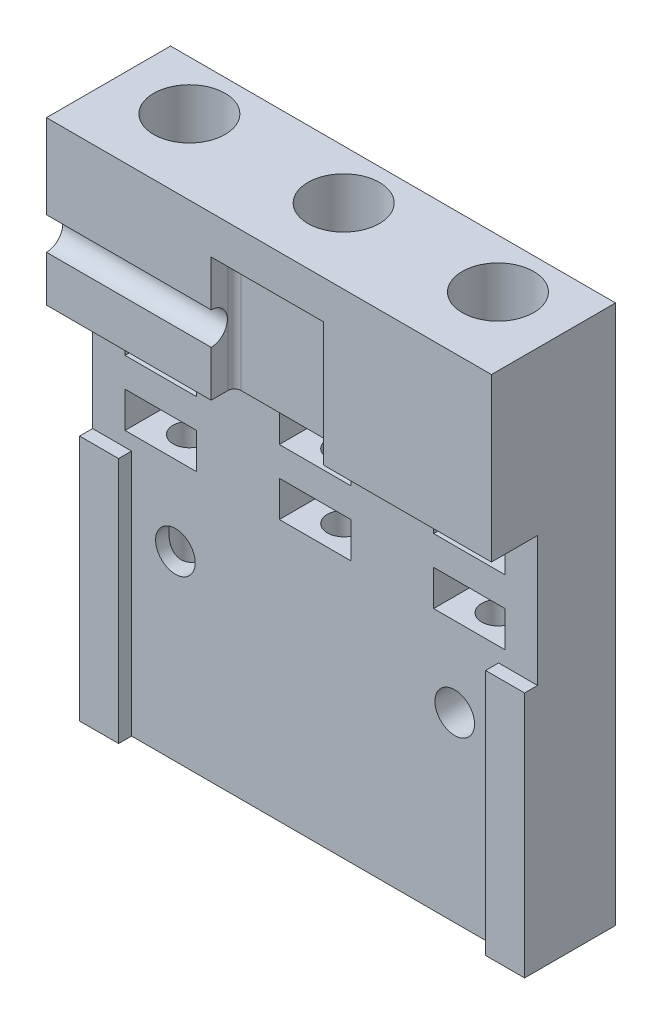
SolidWorks part; units mm, degrees
ref_plane "Plan de face" through (0, 0, 0) normal (0, 0, 1) x (1, 0, 0)
ref_plane "Plan de dessus" through (0, 0, 0) normal (0, 1, 0) x (1, 0, 0)
ref_plane "Plan de droite" through (0, 0, 0) normal (1, 0, 0) x (0, 0, -1)
sketch "Esquisse2" plane through (0, 0, 0) normal (0, 0, 1) x (1, 0, 0)
  line L0 (-28.25, 19) -> (28.25, -19) construction
  line L1 (-28.25, 19) -> (28.25, 19)
  line L2 (-28.25, 19) -> (-28.25, -19)
  line L3 (-28.25, -19) -> (28.25, -19)
  line L4 (28.25, 19) -> (28.25, -19)
  line L5 (0, 0) -> (0, 57.7917) construction
  line L6 (-34.25, 19) -> (-28.25, 19)
  line L8 (-28.25, 19) -> (-28.25, -19)
  line L10 (-34.25, 19) -> (-34.25, -19)
  line L11 (34.25, 19) -> (34.25, -19)
  line L12 (-34.25, -19) -> (-28.25, -19)
  line L13 (28.25, -19) -> (34.25, -19)
  line L14 (28.25, 19) -> (34.25, 19)
  circle A0 centre (-21.5, 9) radius 3.05
  circle A1 centre (21.5, 9) radius 3.05
  point P5 (0, 0)
  dimension "D3" = 6.1
  dimension "D4" = 10
  dimension "D6" = 6
  dimension "D5" = 21.5
  dimension "D1" = 38
  dimension "D2" = 56.5
extrude "SocleSyringe" add sketch "Esquisse2" along normal blind 12 contours L4 L1 L2 L3 A0 A1 | L10 L12 L2 L6 | L14 L4 L13 L11 region at (0, -0.2519, 0) region at (-31.25, 0, 0) region at (31.25, 0, 0)
extrude "Boss.-Extru.2" add sketch "Esquisse2<2>" along normal blind 3 contours A0 | A1 region at (-21.5, 9, 0) region at (21.5, 9, 0)
sketch "Esquisse2<2>" plane through (0, 0, 0) normal (0, 0, 1) x (1, 0, 0) same geometry as "Esquisse2"
extrude "Boss.-Extru.4" add sketch "Esquisse2<4>" along normal offset from surface (14 mm away) 2 contours L10 L12 L2 L6 | L14 L4 L13 L11 region at (-31.25, 0, 0) region at (31.25, 0, 0) up to face at (0, 0, 12) offset beyond the face yes
sketch "Esquisse2<4>" plane through (0, 0, 0) normal (0, 0, 1) x (1, 0, 0) same geometry as "Esquisse2"
sketch "Esquisse3" plane through (0, 0, 0) normal (0, 0, 1) x (1, 0, 0)
  line L0 (-34.25, 39) -> (34.25, 39)
  line L1 (-34.25, 39) -> (-34.25, 19)
  line L2 (-34.25, 19) -> (34.25, 19)
  line L3 (34.25, 39) -> (34.25, 19)
  line L4 (34.25, 19) -> (34.25, -19) construction
  line L5 (-34.25, 19) -> (-34.25, -19) construction
  line L6 (-28.25, 19) -> (28.25, 19) construction
  point P4 (27.9832, -34.9132)
  point P5 (28, 19)
  point P7 (-28, 19)
  point P9 (28, 46.1416)
  point P14 (-34.25, 43.8897)
  dimension "D1" = 20
extrude "Boss.-Extru.3" add sketch "Esquisse3" along normal blind 12
sketch "Esquisse4" plane through (0, 0, 12) normal (0, 0, 1) x (1, 0, 0)
  line L0 (-34.25, 29) -> (34.25, 29) construction
  line L1 (-29.25, 26.75) -> (-18.25, 26.75)
  line L2 (-29.25, 26.75) -> (-29.25, 21.25)
  line L3 (-29.25, 21.25) -> (-18.25, 21.25)
  line L4 (-18.25, 26.75) -> (-18.25, 21.25)
  line L5 (0, 19) -> (0, 39) construction
  line L6 (-29.25, 36.75) -> (-18.25, 36.75)
  line L7 (-18.25, 31.25) -> (-18.25, 36.75)
  line L8 (-34.25, 39) -> (-34.25, 19) construction
  line L9 (34.25, 19) -> (34.25, 39) construction
  line L10 (34.25, 39) -> (-34.25, 39) construction
  line L11 (-29.25, 31.25) -> (-18.25, 31.25)
  line L12 (-29.25, 31.25) -> (-29.25, 36.75)
  line L13 (29.25, 21.25) -> (18.25, 21.25)
  line L14 (18.25, 26.75) -> (18.25, 21.25)
  line L15 (29.25, 26.75) -> (18.25, 26.75)
  line L16 (29.25, 26.75) -> (29.25, 21.25)
  line L17 (29.25, 31.25) -> (29.25, 36.75)
  line L18 (29.25, 31.25) -> (18.25, 31.25)
  line L19 (18.25, 31.25) -> (18.25, 36.75)
  line L20 (29.25, 36.75) -> (18.25, 36.75)
  line L21 (-34.25, 19) -> (34.25, 19)
  line L22 (-34.25, 39) -> (-34.25, 19) construction
  line L23 (34.25, 19) -> (34.25, 39) construction
  line L24 (34.25, 39) -> (-34.25, 39) construction
  line L25 (-5.5, 26.75) -> (-5.5, 21.25)
  line L26 (-34.25, 19) -> (-28.25, 19) construction
  line L27 (-5.5, 36.75) -> (5.5, 36.75)
  line L28 (5.5, 31.25) -> (5.5, 36.75)
  line L29 (-5.5, 31.25) -> (5.5, 31.25)
  line L30 (-5.5, 31.25) -> (-5.5, 36.75)
  line L31 (-5.5, 36.75) -> (5.5, 31.25) construction
  line L32 (-5.5, 26.75) -> (5.5, 26.75)
  line L33 (5.5, 26.75) -> (5.5, 21.25)
  line L34 (-5.5, 21.25) -> (5.5, 21.25)
  point P0 (-29.25, 24)
  point P31 (0, 34)
  point P33 (-18.25, 34)
  point P39 (-5.411, 36.9213)
  dimension "D1" = 5
  dimension "D2" = 10
  dimension "D3" = 11
  dimension "D4" = 5.5
extrude "Enlèv. mat.-Extru.1" cut sketch "Esquisse4" against normal blind 10 contours L12 L11 L7 L6 | L17 L20 L19 L18 | L16 L15 L14 L13 | L4 L1 L2 L3 | L27 L28 L29 L30 | L25 L34 L33 L32 region at (-23.75, 24, 12) region at (-23.75, 34, 12) region at (23.75, 24, 12) region at (23.75, 34, 12)
fillet "Congé1" radius 2.7 12 edges at (-23.75, 36.75, 2) (-23.75, 31.25, 2) (23.75, 21.25, 2) (23.75, 26.75, 2) (23.75, 31.25, 2) (23.75, 36.75, 2) (-23.75, 21.25, 2) (-23.75, 26.75, 2) (0, 26.75, 2) (0, 21.25, 2) (0, 31.25, 2) (0, 36.75, 2)
sketch "Esquisse6" plane through (0, 0, 0) normal (0, 0, 1) x (1, 0, 0)
  line L0 (34.25, 19) -> (34.25, 39) construction
  line L1 (-34.25, 39) -> (34.25, 39)
  line L2 (-34.25, 39) -> (-34.25, 64)
  line L3 (-34.25, 64) -> (34.25, 64)
  line L4 (34.25, 39) -> (34.25, 64)
  dimension "D1" = 25
extrude "Boss.-Extru.5" add sketch "Esquisse6" along normal blind 15.5
sketch "Esquisse7" plane through (0, 0, 15.5) normal (0, 0, 1) x (1, 0, 0)
  line L0 (0, 39) -> (0, 64) construction
  line L1 (34.25, 64) -> (-34.25, 64) construction
  line L2 (-8.9, 39) -> (-8.9, 58.1)
  line L4 (-34.25, 64) -> (-34.25, 39)
  line L5 (-34.25, 39) -> (34.25, 39)
  line L6 (34.25, 39) -> (34.25, 64)
  line L7 (34.25, 64) -> (-34.25, 64)
  line L8 (-34.25, 64) -> (-34.25, 39) construction
  line L9 (-34.25, 39) -> (34.25, 39) construction
  line L10 (34.25, 39) -> (34.25, 64) construction
  line L11 (34.25, 64) -> (-34.25, 64) construction
  line L12 (-8.9, 39) -> (-34.25, 39)
  line L13 (-34.25, 39) -> (-34.25, 64)
  line L14 (-34.25, 64) -> (34.25, 64)
  line L15 (0, 64) -> (0, 58.1)
  line L16 (8.4, 39) -> (34.25, 39)
  line L17 (34.25, 39) -> (34.25, 64)
  line L18 (8.4, 39) -> (8.4, 58.1)
  line L19 (-8.9, 58.1) -> (0, 58.1)
  line L20 (8.4, 58.1) -> (0, 58.1)
  point P14 (8.139, 58.1)
  line M16 (-34.25, 64) -> (-34.25, 39)
  line M17 (-34.25, 39) -> (34.25, 39)
  line M18 (34.25, 39) -> (34.25, 64)
  line M19 (34.25, 64) -> (-34.25, 64)
  dimension "D2" = 8.9
  dimension "D3" = 19.1
  dimension "D4" = 8.4
  dimension "D1" = 0
extrude "Boss.-Extru.6" add sketch "Esquisse7" along normal blind 3.6 contours L2 L19 L15 L14 M16 M17 | L20 L18 L15 M17 M18 M19 region at (-20.2647, 52.2307, 15.5) region at (20.1052, 52.1802, 15.5)
sketch "Esquisse8" plane through (-8.9, 0, 0) normal (1, 0, 0) x (0, 0, -1)
  line L0 (-19.1, 39) -> (-19.1, 64) construction
  line L1 (-19.1, 51.05) -> (-19.1, 46.05)
  line L2 (-19.1, 39) -> (-19.1, 58.1) construction
  line L3 (-19.1, 39) -> (-19.1, 58.1) construction
  arc A0 (-19.1, 51.05) -> (-19.1, 46.05) centre (-19.1, 48.55) cw
  dimension "D1" = 5
extrude "Enlèv. mat.-Extru.3" cut sketch "Esquisse8" against normal through all
fillet "Congé2" radius 1 2 edges at (8.4, 48.55, 15.5) (-8.9, 48.55, 15.5)
sketch "Esquisse5" plane through (0, 0, 0) normal (0, 1, 0) x (1, 0, 0)
  line L0 (29.25, -12) -> (18.25, -12) construction
  line L1 (29.25, -12) -> (18.25, -12) construction
  line L2 (0, 0) -> (0, -26.6793) construction
  circle A0 centre (23.75, -7.6) radius 2.5
  circle A1 centre (-23.75, -7.6) radius 2.5
  circle A2 centre (0, -7.6) radius 2.5
  point P5 (23.75, -12)
  point P12 (0, -7.1351)
  point P13 (0, 0)
  dimension "D1" = 5
  dimension "D2" = 4.4
extrude "Enlèv. mat.-Extru.2" cut sketch "Esquisse5" against normal through all both and the other way through all
sketch "Esquisse9" plane through (0, 64, 0) normal (0, 1, 0) x (1, 0, 0)
  circle A24 centre (-23.75, -7.6) radius 5.5
  circle A25 centre (-23.75, -7.6) radius 5.5
  circle A27 centre (0, -7.6) radius 5.5
  circle A28 centre (0, -7.6) radius 5.5
  circle A30 centre (23.75, -7.6) radius 5.5
  circle A31 centre (23.75, -7.6) radius 5.5
  dimension "D1" = 3
  dimension "D2" = 3
  dimension "D3" = 3
extrude "Enlèv. mat.-Extru.4" cut sketch "Esquisse9" against normal offset from surface (24 mm away) 1 up to face at (-0.15, 39, 16.3986)
